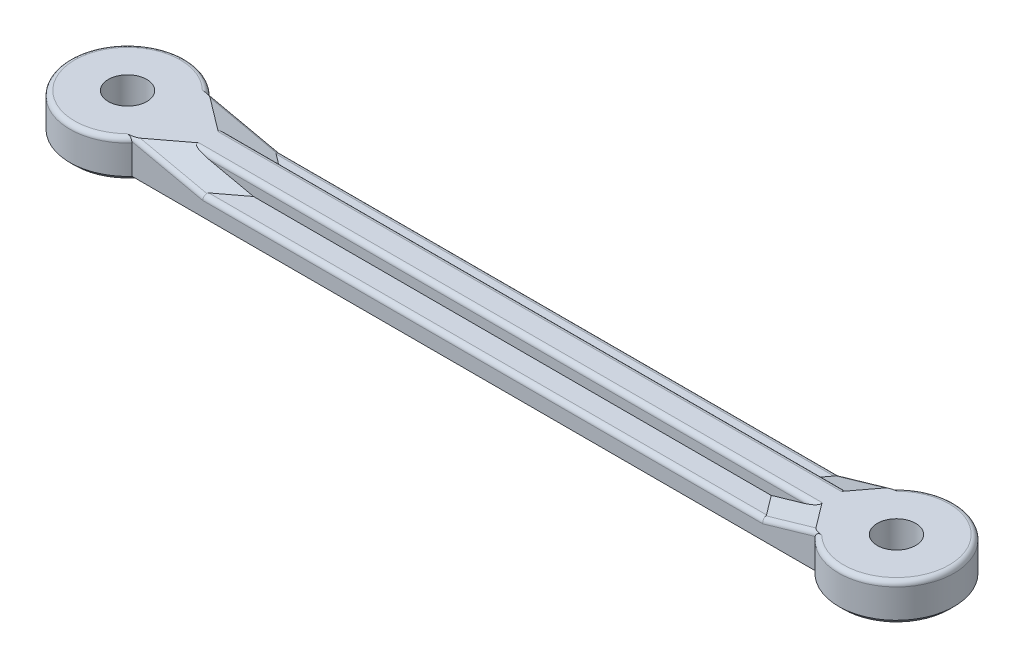
SolidWorks part; units mm, degrees
ref_plane "Front Plane" through (0, 0, 0) normal (0, 0, 1) x (1, 0, 0)
ref_plane "Top Plane" through (0, 0, 0) normal (0, 1, 0) x (1, 0, 0)
ref_plane "Right Plane" through (0, 0, 0) normal (1, 0, 0) x (0, 0, -1)
sketch "Sketch1" plane through (0, 0, 0) normal (0, 1, 0) x (1, 0, 0)
  line L0 (-23.7762, 0) -> (56.2238, 0) construction
  line L1 (-19.304, 4) -> (51.7517, 4)
  line L3 (-19.304, -4) -> (51.7517, -4)
  circle A0 centre (-23.7762, 0) radius 2
  circle A1 centre (56.2238, 0) radius 2
  arc A2 (-19.304, 4) -> (-19.304, -4) centre (-23.7762, 0) ccw
  arc A3 (51.7517, -4) -> (51.7517, 4) centre (56.2238, 0) ccw
  dimension "D1" = 4
  dimension "D2" = 4
  dimension "D4" = 12
  dimension "D5" = 12
  dimension "D7" = 8
  dimension "D6" = 23.7762
  dimension "D3" = 80
  dimension "D8" = 71.0557
extrude "Boss-Extrude1" add sketch "Sketch1" along normal blind 4
sketch "Sketch2" plane through (0, 4, 0) normal (0, 1, 0) x (1, 0, 0)
  line L0 (-19.304, -4) -> (-16.0004, -1.5)
  line L1 (-16.0004, -1.5) -> (49.8599, -1.5)
  line L2 (49.8599, -1.5) -> (51.7517, -4)
  line L3 (-19.304, -4) -> (51.7517, -4) construction
  line L4 (-23.7762, 0) -> (56.2238, 0) construction
  line L5 (-19.304, -4) -> (51.7517, -4)
  line L6 (49.8599, 1.5) -> (51.7517, 4)
  line L7 (-16.0004, 1.5) -> (49.8599, 1.5)
  line L8 (-19.304, 4) -> (-16.0004, 1.5)
  line L9 (-19.304, 4) -> (51.7517, 4)
  dimension "D1" = 2.5
  dimension "D2" = 37.116
extrude "Cut-Extrude1" cut sketch "Sketch2" against normal blind 1.5
chamfer "Chamfer2" distance 1.5 angle 70 1 edges at (50.8058, 2.5, -2.75) first distance on face at (50.8058, 3.25, -2.75)
chamfer "Chamfer4" distance 0.5 angle 45 4 edges at (-29.7762, 0, 0) (16.2238, 0, 4) (62.2238, 0, 0) (16.2238, 0, -4)
chamfer "Chamfer5" distance 1.5 angle 70 1 edges at (-17.6522, 2.5, -2.75) first distance on face at (-17.6522, 3.25, -2.75)
chamfer "Chamfer6" distance 1.5 angle 70 2 edges at (-17.6522, 2.5, 2.75) (50.8058, 2.5, 2.75) first distance on face at (-17.6522, 3.25, 2.75) first distance on face at (50.8058, 3.25, 2.75)
fillet "Fillet3" radius 0.5 2 edges at (62.2238, 4, 0) (-29.7762, 4, 0)
fillet "Fillet4" radius 0.5 6 edges at (-15.8892, 3.25, 4) (17.0545, 2.5, 4) (49.1676, 3.25, 4) (-15.8892, 3.25, -4) (17.0545, 2.5, -4) (49.1676, 3.25, -4)
fillet "Fillet5" radius 0.5 2 edges at (16.9297, 4, 1.5) (16.9297, 4, -1.5)
